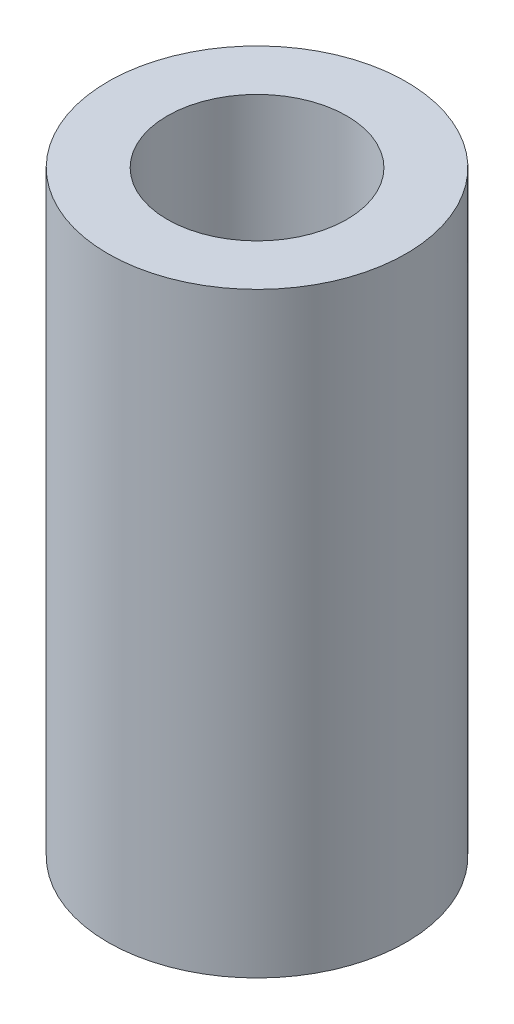
SolidWorks part; units mm, degrees
material "Cast Alloy Steel"
ref_plane "Front Plane" through (0, 0, 0) normal (0, 0, 1) x (1, 0, 0)
ref_plane "Top Plane" through (0, 0, 0) normal (0, 1, 0) x (1, 0, 0)
ref_plane "Right Plane" through (0, 0, 0) normal (1, 0, 0) x (0, 0, -1)
sketch "Sketch1" plane through (0, 0, 0) normal (0, 1, 0) x (1, 0, 0)
  circle A0 centre (0, 0) radius 15.05
  circle A1 centre (0, 0) radius 25
  dimension "D1" = 30.1
  dimension "D2" = 50
extrude "Boss-Extrude1" add sketch "Sketch1" along normal blind 100
